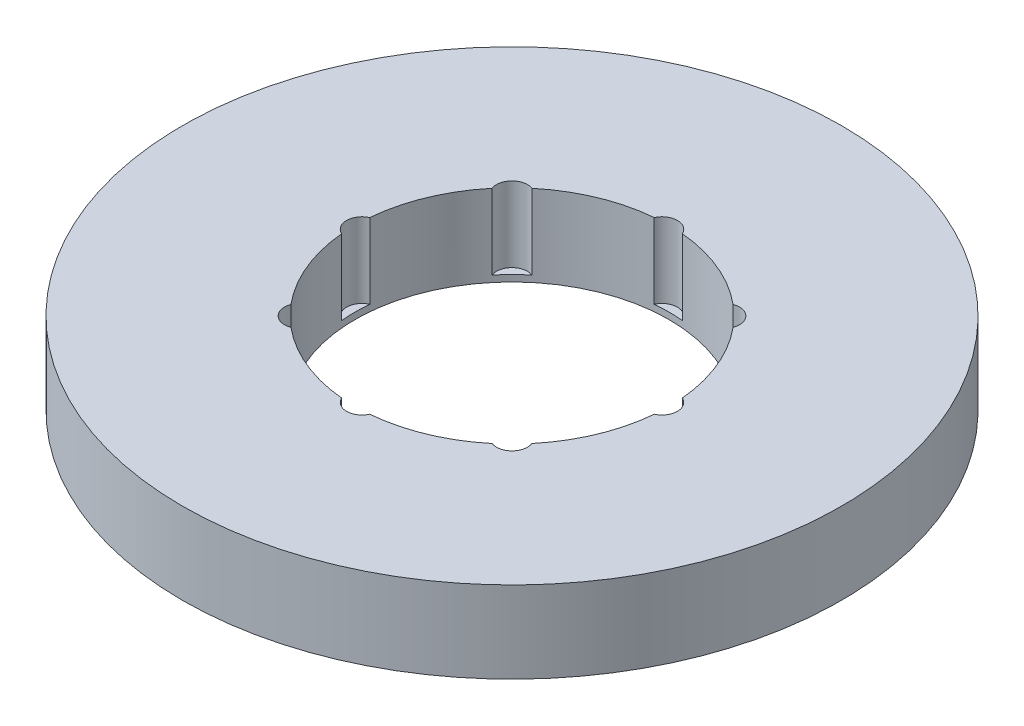
SolidWorks part; units mm, degrees
ref_plane "Front Plane" through (0, 0, 0) normal (0, 0, 1) x (1, 0, 0)
ref_plane "Top Plane" through (0, 0, 0) normal (0, 1, 0) x (1, 0, 0)
ref_plane "Right Plane" through (0, 0, 0) normal (1, 0, 0) x (0, 0, -1)
sketch "Sketch1" plane through (0, 0, 0) normal (0, 1, 0) x (1, 0, 0)
  circle A0 centre (0, 0) radius 52.5
  dimension "FLANGE_OD" = 105
extrude "Boss-Extrude1" add sketch "Sketch1" along normal blind 13
sketch "Sketch2" plane through (0, 0, 0) normal (0, 1, 0) x (1, 0, 0)
  circle A0 centre (0, 0) radius 25
  dimension "BORE_D" = 50
extrude "Cut-Extrude1" cut sketch "Sketch2" along normal through all
sketch "Sketch3" plane through (0, 13, 0) normal (0, 1, 0) x (1, 0, 0)
  circle A0 centre (0, 0) radius 23.8825 construction
  circle A1 centre (-23.8825, 0) radius 2.4606
  dimension "BOLT_D" = 4.9211
  dimension "BOLT_PCD" = 47.7651
extrude "Cut-Extrude2" cut sketch "Sketch3" against normal blind 11.9675
pattern_circular "CirPattern1" count 8 over 360 about axis through (0, 0, 0) along (0, 1, 0) of "Cut-Extrude2"
